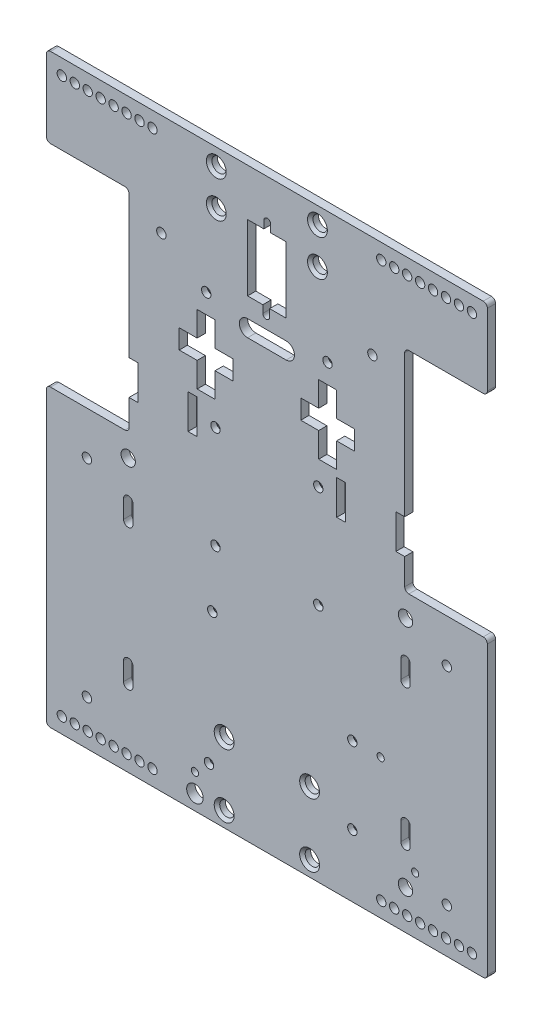
SolidWorks part; units mm, degrees
ref_plane "Front Plane" through (0, 0, 0) normal (0, 0, 1) x (1, 0, 0)
ref_plane "Top Plane" through (0, 0, 0) normal (0, 1, 0) x (1, 0, 0)
ref_plane "Right Plane" through (0, 0, 0) normal (1, 0, 0) x (0, 0, -1)
sketch "Sketch1" plane through (0, 0, 0) normal (0, 0, 1) x (1, 0, 0)
  line L0 (0, 103.7745) -> (0, -122.5392) construction
  line L1 (-241.098, -9.3824) -> (295.6863, -9.3824) construction
  line L2 (-80, -100.3627) -> (80, -100.3627)
  line L3 (80, -100.3627) -> (80, 6.6373)
  line L4 (80, 6.6373) -> (50, 6.6373)
  line L5 (50, 6.6373) -> (50, 83.1373)
  line L6 (50, 83.1373) -> (80, 83.1373)
  line L7 (80, 83.1373) -> (80, 112.1373)
  line L8 (80, 112.1373) -> (-80, 112.1373)
  line L9 (-80, -100.3627) -> (-80, 6.6373)
  line L10 (-80, 6.6373) -> (-50, 6.6373)
  line L11 (-50, 6.6373) -> (-50, 83.1373)
  line L12 (-50, 83.1373) -> (-80, 83.1373)
  line L13 (-80, 83.1373) -> (-80, 112.1373)
  point P14 (0, -100.3627)
  point P19 (0, 112.1373)
  dimension "D1" = 29
  dimension "D2" = 76.5
  dimension "D3" = 107
  dimension "D4" = 160
  dimension "D5" = 30
  dimension "D6" = 30
extrude "Boss-Extrude1" add sketch "Sketch1" along normal blind 3
sketch "Sketch2" plane through (0, 0, 0) normal (0, 0, -1) x (-1, 0, 0)
  line L0 (0, 75.1311) -> (0, 87.1311) construction
  line L1 (-133.8252, 10.7921) -> (150.4053, 10.7921) construction
  line L2 (-7, 95.0453) -> (-1.3739, 95.0453)
  line L3 (7, 95.0453) -> (7, 71.0453)
  line L4 (7, 71.0453) -> (1.4697, 71.0453)
  line L5 (-7, 95.0453) -> (-7, 71.0453)
  line L7 (-1.3739, 97.7783) -> (-1.3739, 95.0453)
  line L8 (1.0943, 97.7783) -> (1.0943, 95.0453)
  line L9 (0, 0) -> (0, 124.4997) construction
  line L10 (1.4697, 68.3124) -> (1.4697, 71.0453)
  line L11 (-0.9985, 68.3124) -> (-0.9985, 71.0453)
  line L12 (1.0943, 95.0453) -> (7, 95.0453)
  line L13 (-0.9985, 71.0453) -> (-7, 71.0453)
  arc A0 (1.0943, 97.7783) -> (-1.3739, 97.7783) centre (-0.1398, 97.7783) ccw
  arc A1 (1.4697, 68.3124) -> (-0.9985, 68.3124) centre (0.2356, 68.3124) cw
  circle A2 centre (38.2796, 75.1373) radius 1.7
  circle A3 centre (-38.2796, 75.1373) radius 1.7
  point P10 (0, 75.1373)
  point P11 (0, 99.1373)
  dimension "D2" = 14
  dimension "D3" = 24
extrude "Cut-Extrude1" cut sketch "Sketch2" against normal blind 3
sketch "Sketch3" plane through (0, 0, 3) normal (0, 0, 1) x (1, 0, 0)
  line L0 (0, 161.5948) -> (0, -130.4668) construction
  line L3 (-7, 60.8964) -> (7, 60.8964) construction
  line L4 (-7, 63.8964) -> (7, 63.8964)
  line L5 (-7, 57.8964) -> (7, 57.8964)
  circle A1 centre (-22, 64.6804) radius 1.7
  circle A2 centre (22, 64.6804) radius 1.7
  arc A3 (-7, 63.8964) -> (-7, 57.8964) centre (-7, 60.8964) ccw
  arc A4 (7, 57.8964) -> (7, 63.8964) centre (7, 60.8964) ccw
  point P15 (0, 60.8964)
  dimension "D2" = 44
  dimension "D3" = 14
extrude "Cut-Extrude2" cut sketch "Sketch3" against normal blind 3
sketch "Sketch4" plane through (0, 0, 3) normal (0, 0, 1) x (1, 0, 0)
  line L0 (0, 119.8519) -> (0, 60.8576) construction
  line L1 (80, 83.1373) -> (80, 112.1373) construction
  line L3 (80, 112.1373) -> (-80, 112.1373) construction
  line L4 (104.1126, 106.5373) -> (-21.9204, 106.5373) construction
  line L5 (-144.8224, 0) -> (150.0768, 0) construction
  line L6 (-113.8427, 6.6373) -> (99.251, 6.6373) construction
  line L7 (-80, -100.3627) -> (80, -100.3627) construction
  line L8 (-80, 6.6373) -> (-80, -100.3627) construction
  line L9 (-130.8506, -94.7627) -> (-23.3076, -94.7627) construction
  line L10 (-74.4, -94.7627) -> (-69.7, -94.7627) construction
  circle A0 centre (74.4, 106.5373) radius 1.7
  circle A1 centre (69.7, 106.5373) radius 1.7
  circle A2 centre (65, 106.5373) radius 1.7
  circle A3 centre (60.3, 106.5373) radius 1.7
  circle A4 centre (55.6, 106.5373) radius 1.7
  circle A5 centre (50.9, 106.5373) radius 1.7
  circle A6 centre (46.2, 106.5373) radius 1.7
  circle A7 centre (41.5, 106.5373) radius 1.7
  circle A8 centre (-74.4, 106.5373) radius 1.7
  circle A9 centre (-69.7, 106.5373) radius 1.7
  circle A10 centre (-65, 106.5373) radius 1.7
  circle A11 centre (-60.3, 106.5373) radius 1.7
  circle A12 centre (-55.6, 106.5373) radius 1.7
  circle A13 centre (-50.9, 106.5373) radius 1.7
  circle A14 centre (-46.2, 106.5373) radius 1.7
  circle A15 centre (-41.5, 106.5373) radius 1.7
  circle A16 centre (-74.4, -94.7627) radius 1.7
  circle A17 centre (-69.7, -94.7627) radius 1.7
  circle A18 centre (-65, -94.7627) radius 1.7
  circle A19 centre (-60.3, -94.7627) radius 1.7
  circle A20 centre (-55.6, -94.7627) radius 1.7
  circle A21 centre (-50.9, -94.7627) radius 1.7
  circle A22 centre (-46.2, -94.7627) radius 1.7
  circle A23 centre (-41.5, -94.7627) radius 1.7
  circle A24 centre (41.5, -94.7627) radius 1.7
  circle A25 centre (46.2, -94.7627) radius 1.7
  circle A26 centre (50.9, -94.7627) radius 1.7
  circle A27 centre (55.6, -94.7627) radius 1.7
  circle A28 centre (60.3, -94.7627) radius 1.7
  circle A29 centre (65, -94.7627) radius 1.7
  circle A30 centre (69.7, -94.7627) radius 1.7
  circle A31 centre (74.4, -94.7627) radius 1.7
  dimension "D1" = 5.6
  dimension "D2" = 5.6
  dimension "D3" = 8
  dimension "D4" = 5.6
  dimension "D5" = 5.6
  dimension "D6" = 8
extrude "Cut-Extrude3" cut sketch "Sketch4" against normal blind 3
sketch "Sketch6" plane through (0, 0, 0) normal (0, 0, 1) x (1, 0, 0)
  line L0 (0, 117.4623) -> (0, -109.6474) construction
  line L1 (142.8274, 0) -> (-149.0496, 0) construction
  line L2 (25.3, 57.6373) -> (18.8, 57.6373)
  line L3 (18.8, 57.6373) -> (18.8, 48.6373)
  line L4 (18.8, 48.6373) -> (12.3, 48.6373)
  line L5 (12.3, 48.6373) -> (12.3, 41.6373)
  line L6 (12.3, 41.6373) -> (18.8, 41.6373)
  line L7 (18.8, 41.6373) -> (18.8, 32.6373)
  line L8 (18.8, 32.6373) -> (25.3, 32.6373)
  line L9 (25.3, 32.6373) -> (25.3, 41.6373)
  line L10 (25.3, 41.6373) -> (31.8, 41.6373)
  line L11 (31.8, 41.6373) -> (31.8, 48.6373)
  line L12 (31.8, 48.6373) -> (25.3, 48.6373)
  line L13 (25.3, 48.6373) -> (25.3, 57.6373)
  line L14 (80, 112.1373) -> (-80, 112.1373) construction
  line L15 (-31.8, 48.6373) -> (-25.3, 48.6373)
  line L16 (22.05, 25.7267) -> (22.05, 72.8258) construction
  line L17 (39.5883, 45.1373) -> (1.8205, 45.1373) construction
  line L18 (-31.8, 41.6373) -> (-31.8, 48.6373)
  line L19 (-25.3, 41.6373) -> (-31.8, 41.6373)
  line L20 (-25.3, 32.6373) -> (-25.3, 41.6373)
  line L21 (-18.8, 32.6373) -> (-25.3, 32.6373)
  line L22 (-18.8, 41.6373) -> (-18.8, 32.6373)
  line L23 (-12.3, 41.6373) -> (-18.8, 41.6373)
  line L24 (-12.3, 48.6373) -> (-12.3, 41.6373)
  line L25 (-18.8, 48.6373) -> (-12.3, 48.6373)
  line L26 (-18.8, 57.6373) -> (-18.8, 48.6373)
  line L27 (-25.3, 57.6373) -> (-18.8, 57.6373)
  line L28 (-25.3, 48.6373) -> (-25.3, 57.6373)
  line L29 (50, 6.6373) -> (50, 83.1373) construction
  dimension "D1" = 54.5
  dimension "D2" = 25
  dimension "D3" = 19.5
  dimension "D4" = 6.5
  dimension "D5" = 6.5
  dimension "D6" = 7
  dimension "D7" = 24.7
extrude "Cut-Extrude6" cut sketch "Sketch6" along normal blind 3
fillet "Fillet1" radius 1.5 4 edges at (80, 83.1373, 1.5) (80, 112.1373, 1.5) (-80, 112.1373, 1.5) (-80, 83.1373, 1.5)
fillet "Fillet2" radius 1.5 2 edges at (80, -100.3627, 1.5) (-80, -100.3627, 1.5)
sketch "Sketch7" plane through (0, 0, 3) normal (0, 0, 1) x (1, 0, 0)
  line L0 (0, 119.4421) -> (0, -115.5867) construction
  line L1 (-78.5, -100.3627) -> (78.5, -100.3627) construction
  circle A0 centre (-15.5, -94.8627) radius 2.6
  circle A1 centre (-15.5, -71.8627) radius 2.6
  circle A2 centre (15.5, -94.8627) radius 2.6
  circle A3 centre (15.5, -71.8627) radius 2.6
  dimension "D1" = 5.5
  dimension "D2" = 23
  dimension "D4" = 31
  dimension "D5" = 5.2
  dimension "D6" = 5.2
  dimension "D3" = 31
extrude "Cut-Extrude7" cut sketch "Sketch7" against normal blind 3
sketch "Sketch8" plane through (0, 0, 0) normal (0, 0, 1) x (1, 0, 0)
  line L0 (-50, 30.1373) -> (-46.8, 30.1373)
  line L1 (-50, 83.1373) -> (-50, 6.6373) construction
  line L2 (-46.8, 30.1373) -> (-46.8, 17.6373)
  line L3 (-46.8, 17.6373) -> (-50, 17.6373)
  line L4 (-50, 17.6373) -> (-50, 30.1373)
  line L5 (-50, 6.6373) -> (-80, 6.6373) construction
  line L6 (0, 37.5967) -> (0, -16.6739) construction
  line L7 (46.8, 17.6373) -> (50, 17.6373)
  line L8 (50, 30.1373) -> (46.8, 30.1373)
  line L9 (50, 17.6373) -> (50, 30.1373)
  line L10 (46.8, 30.1373) -> (46.8, 17.6373)
  line L11 (-50, 23.8873) -> (-9.1631, 23.8873) construction
  dimension "D1" = 11
  dimension "D2" = 12.5
  dimension "D3" = 3.2
extrude "Cut-Extrude9" cut sketch "Sketch8" along normal blind 3
sketch "Sketch9" plane through (0, 0, 3) normal (0, 0, 1) x (1, 0, 0)
  line L0 (0, 47.1979) -> (0, -24.6531) construction
  line L1 (-46.8, 23.8873) -> (46.8, 23.8873) construction
  line L2 (-46.8, 17.6373) -> (-46.8, 30.1373) construction
  line L3 (46.8, 30.1373) -> (46.8, 17.6373) construction
  line L4 (-46.8, 30.1373) -> (46.8, 30.1373) construction
  line L5 (-46.8, 17.6373) -> (46.8, 17.6373) construction
  line L6 (-28.6, 30.1373) -> (-28.6, 17.6373)
  line L7 (-28.6, 17.6373) -> (-25.35, 17.6373)
  line L8 (-25.35, 17.6373) -> (-25.35, 30.1373)
  line L9 (-25.35, 30.1373) -> (-28.6, 30.1373)
  line L10 (28.6, 17.6373) -> (25.35, 17.6373)
  line L11 (25.35, 17.6373) -> (25.35, 30.1373)
  line L12 (25.35, 30.1373) -> (28.6, 30.1373)
  line L13 (28.6, 30.1373) -> (28.6, 17.6373)
  dimension "D1" = 3.25
  dimension "D2" = 18.2
extrude "Cut-Extrude10" cut sketch "Sketch9" against normal blind 3
sketch "Sketch10" plane through (0, 0, 0) normal (0, 0, 1) x (1, 0, 0)
  line L0 (0, 32.0487) -> (0, -85.0415) construction
  line L1 (-112.565, 0) -> (146.2213, 0) construction
  line L2 (-80, 6.6373) -> (-80, -98.8627) construction
  line L3 (-50.3, -15.0627) -> (-50.3, -21.6627) construction
  line L4 (-48.6, -15.0627) -> (-48.6, -21.6627)
  line L5 (-52, -15.0627) -> (-52, -21.6627)
  line L6 (-50, 32.1373) -> (-50, -164.0413) construction
  line L7 (-52, -66.0627) -> (-52, -72.6627)
  line L8 (-50, 6.6373) -> (-80, 6.6373) construction
  line L9 (-48.6, -66.0627) -> (-48.6, -72.6627)
  line L10 (-50.3, -66.0627) -> (-50.3, -72.6627) construction
  line L11 (-50, 83.1373) -> (-50, 32.1373) construction
  line L12 (50.3, -66.0627) -> (50.3, -72.6627) construction
  line L13 (48.6, -66.0627) -> (48.6, -72.6627)
  line L14 (52, -66.0627) -> (52, -72.6627)
  line L15 (50.3, -15.0627) -> (50.3, -21.6627) construction
  line L16 (48.6, -15.0627) -> (48.6, -21.6627)
  line L17 (52, -15.0627) -> (52, -21.6627)
  arc A0 (-48.6, -15.0627) -> (-52, -15.0627) centre (-50.3, -15.0627) ccw
  arc A1 (-52, -21.6627) -> (-48.6, -21.6627) centre (-50.3, -21.6627) ccw
  arc A2 (-48.6, -66.0627) -> (-52, -66.0627) centre (-50.3, -66.0627) ccw
  arc A3 (-52, -72.6627) -> (-48.6, -72.6627) centre (-50.3, -72.6627) ccw
  arc A4 (48.6, -66.0627) -> (52, -66.0627) centre (50.3, -66.0627) cw
  arc A5 (52, -72.6627) -> (48.6, -72.6627) centre (50.3, -72.6627) cw
  arc A6 (48.6, -15.0627) -> (52, -15.0627) centre (50.3, -15.0627) cw
  arc A7 (52, -21.6627) -> (48.6, -21.6627) centre (50.3, -21.6627) cw
  point P10 (-50.3, -18.3627)
  point P23 (-50.3, -69.3627)
  point P30 (50.3, -69.3627)
  point P37 (50.3, -18.3627)
  dimension "D1" = 20
  dimension "D2" = 10
  dimension "D5" = 28
  dimension "D4" = 51
  dimension "D6" = 3.4
  dimension "D3" = 2
extrude "Cut-Extrude12" cut sketch "Sketch10" along normal blind 3
sketch "Sketch11" plane through (0, 0, 0) normal (0, 0, 1) x (1, 0, 0)
  line L0 (0, 120.896) -> (0, -114.7225) construction
  line L1 (-147.8474, 0) -> (160.9193, 0) construction
  line L2 (-25.35, 23.8873) -> (25.35, 23.8873) construction
  line L3 (-25.35, 17.6373) -> (-25.35, 30.1373) construction
  line L4 (25.35, 30.1373) -> (25.35, 17.6373) construction
  circle A0 centre (-18.65, 23.8873) radius 1.7
  circle A1 centre (-18.65, -13.3127) radius 1.7
  circle A2 centre (18.65, -13.3127) radius 1.7
  circle A3 centre (18.65, 23.8873) radius 1.7
  dimension "D1" = 5
  dimension "D2" = 3.4
  dimension "D3" = 5
extrude "Cut-Extrude14" cut sketch "Sketch11" along normal blind 3
sketch "Sketch12" plane through (0, 0, 0) normal (0, 0, 1) x (1, 0, 0)
  line L0 (0, 118.5936) -> (0, -114.7383) construction
  line L1 (-119.07, 1.9277) -> (166.0192, 1.9277) construction
  line L4 (80, 6.6373) -> (50, 6.6373) construction
  line L6 (80, -98.8627) -> (80, 6.6373) construction
  line L7 (-78.5, -100.3627) -> (78.5, -100.3627) construction
  circle A0 centre (65.3, -9.0627) radius 1.7
  circle A1 centre (-65.3, -9.0627) radius 1.7
  circle A2 centre (65.3, -84.1627) radius 1.7
  circle A3 centre (-65.3, -84.1627) radius 1.7
  dimension "D1" = 14
  dimension "D2" = 13
  dimension "D3" = 13
  dimension "D4" = 14.5
extrude "Cut-Extrude16" cut sketch "Sketch12" along normal blind 3
sketch "Sketch13" plane through (0, 0, 0) normal (0, 0, 1) x (1, 0, 0)
  line L0 (0, 95.119) -> (0, -115.5867) construction
  line L1 (-133.2113, 0) -> (163.1909, 0) construction
  line L3 (-78.5, -100.3627) -> (78.5, -100.3627) construction
  line L4 (-80, 6.6373) -> (-80, -98.8627) construction
  circle A0 centre (-21, -82.8627) radius 1.7
  circle A2 centre (31, -77.6627) radius 1.7
  circle A3 centre (31, -49.7627) radius 1.7
  circle A4 centre (-19.8, -34.5627) radius 1.7
  dimension "D1" = 17.5
  dimension "D3" = 5.2
  dimension "D5" = 27.9
  dimension "D6" = 50.8
  dimension "D2" = 59
  dimension "D4" = 52
  dimension "D7" = 48.3
extrude "Cut-Extrude18" cut sketch "Sketch13" along normal blind 3
sketch "Sketch14" plane through (0, 0, 0) normal (0, 0, 1) x (1, 0, 0)
  line L0 (0, 14.3859) -> (0, -107.2008) construction
  line L3 (80, -98.8627) -> (80, 6.6373) construction
  circle A1 centre (53.8, -79.7627) radius 1.3
  circle A2 centre (41.3, -49.7627) radius 1.3
  dimension "D1" = 40
  dimension "D2" = 30
  dimension "D3" = 12.5
extrude "Cut-Extrude20" cut sketch "Sketch14" along normal blind 3
sketch "Sketch15" plane through (0, 0, 0) normal (0, 0, 1) x (1, 0, 0)
  line L0 (0, 37.8305) -> (0, -61.1397) construction
  line L1 (-57.516, 0) -> (91.2068, 0) construction
  line L2 (50.3, -23.3627) -> (50.3, -64.3627) construction
  line L3 (50.3, -43.8627) -> (-40.3092, -43.8627) construction
  line L4 (50.3, -23.3627) -> (50.3, 36.7606) construction
  line L5 (50.3, -13.3627) -> (101.0147, -13.3627) construction
  arc A0 (48.6, -21.6627) -> (52, -21.6627) centre (50.3, -21.6627) ccw construction
  circle A1 centre (50.3, -1.5627) radius 2.6
  arc A2 (52, -15.0627) -> (48.6, -15.0627) centre (50.3, -15.0627) ccw construction
  circle A3 centre (-50.3, -1.5627) radius 2.6
  arc A4 (52, -66.0627) -> (48.6, -66.0627) centre (50.3, -66.0627) ccw construction
  circle A5 centre (50.3, -86.1627) radius 2.6
  dimension "D1" = 9.2
extrude "Cut-Extrude21" cut sketch "Sketch15" along normal blind 10
sketch "Sketch16" plane through (0, 0, 3) normal (0, 0, 1) x (1, 0, 0)
  line L0 (-15.5, -94.8627) -> (-15.5, -30.8074) construction
  line L1 (-18.1, -94.8627) -> (-18.1, -49.3742) construction
  line L2 (-26.1, -91.8627) -> (-4.2475, -91.8627) construction
  circle A0 centre (-15.5, -94.8627) radius 2.6 construction
  circle A1 centre (-26.1, -94.8627) radius 3
  circle A2 centre (-26.1, -88.0627) radius 1.3
  dimension "D1" = 5
  dimension "D2" = 2.5
extrude "Cut-Extrude24" cut sketch "Sketch16" against normal blind 10
chamfer "Chamfer1" distance 1 angle 45 1 edges at (-12.9, -71.8627, 3)
chamfer "Chamfer2" distance 1 angle 45 1 edges at (12.9, -71.8627, 3)
chamfer "Chamfer3" distance 1 angle 45 1 edges at (-12.9, -94.8627, 3)
chamfer "Chamfer4" distance 1 angle 45 1 edges at (12.9, -94.8627, 3)
chamfer "Chamfer5" distance 1 angle 45 1 edges at (20.35, 23.8873, 0)
chamfer "Chamfer6" distance 1 angle 45 1 edges at (-16.95, 23.8873, 0)
chamfer "Chamfer7" distance 1 angle 45 1 edges at (20.35, -13.3127, 0)
chamfer "Chamfer8" distance 1 angle 45 1 edges at (-16.95, -13.3127, 0)
chamfer "Chamfer9" distance 1 angle 45 1 edges at (-18.1, -34.5627, 0)
chamfer "Chamfer10" distance 1 angle 45 1 edges at (32.7, -49.7627, 0)
chamfer "Chamfer11" distance 1 angle 45 1 edges at (32.7, -77.6627, 0)
chamfer "Chamfer12" distance 1 angle 45 1 edges at (-19.3, -82.8627, 0)
sketch "Sketch17" plane through (0, 0, 0) normal (0, 0, 1) x (1, 0, 0)
  line L0 (0, 228.2407) -> (0, 55.0266) construction
  line L1 (-113.4269, 141.6336) -> (115.0781, 141.6336) construction
  line L2 (41.5, 106.5373) -> (41.5, 201.3982) construction
  line L3 (-41.5, 106.5373) -> (-41.5, 205.9867) construction
  line L4 (-46.2, 106.5373) -> (-46.2, 205.9867) construction
  line L5 (46.2, 106.5373) -> (46.2, 201.3982) construction
  line L6 (0, 112.1373) -> (0, 87.6373) construction
  line L7 (78.5, 112.1373) -> (-78.5, 112.1373) construction
  line L8 (-18.35, 103.4373) -> (17.8418, 103.4373) construction
  circle A0 centre (-18.35, 106.0373) radius 2.6
  circle A1 centre (-18.35, 92.8373) radius 2.6
  circle A2 centre (18.35, 92.8373) radius 2.6
  circle A3 centre (18.35, 106.0373) radius 2.6
  dimension "D1" = 24.5
  dimension "D2" = 3.5
  dimension "D3" = 8
  dimension "D4" = 15.75
extrude "Cut-Extrude27" cut sketch "Sketch17" along normal blind 10
fillet "Fillet3" radius 1.5 1 edges at (80, 6.6373, 1.5)
fillet "Fillet4" radius 1.5 1 edges at (-80, 6.6373, 1.5)
chamfer "Chamfer13" distance 1 angle 45 1 edges at (-15.75, 106.0373, 3)
chamfer "Chamfer14" distance 1 angle 45 1 edges at (20.95, 106.0373, 3)
chamfer "Chamfer15" distance 1 angle 45 1 edges at (-15.75, 92.8373, 3)
chamfer "Chamfer16" distance 1 angle 45 1 edges at (20.95, 92.8373, 3)
chamfer "Chamfer17" distance 1 angle 45 1 edges at (-20.3, 64.6804, 0)
chamfer "Chamfer18" distance 1 angle 45 1 edges at (20.3, 64.6804, 0)
fillet "Fillet5" radius 1.5 1 edges at (50, 6.6373, 1.5)
fillet "Fillet6" radius 1.5 1 edges at (50, 83.1373, 1.5)
fillet "Fillet7" radius 1.5 1 edges at (-50, 83.1373, 1.5)
fillet "Fillet8" radius 1.5 1 edges at (-50, 6.6373, 1.5)
